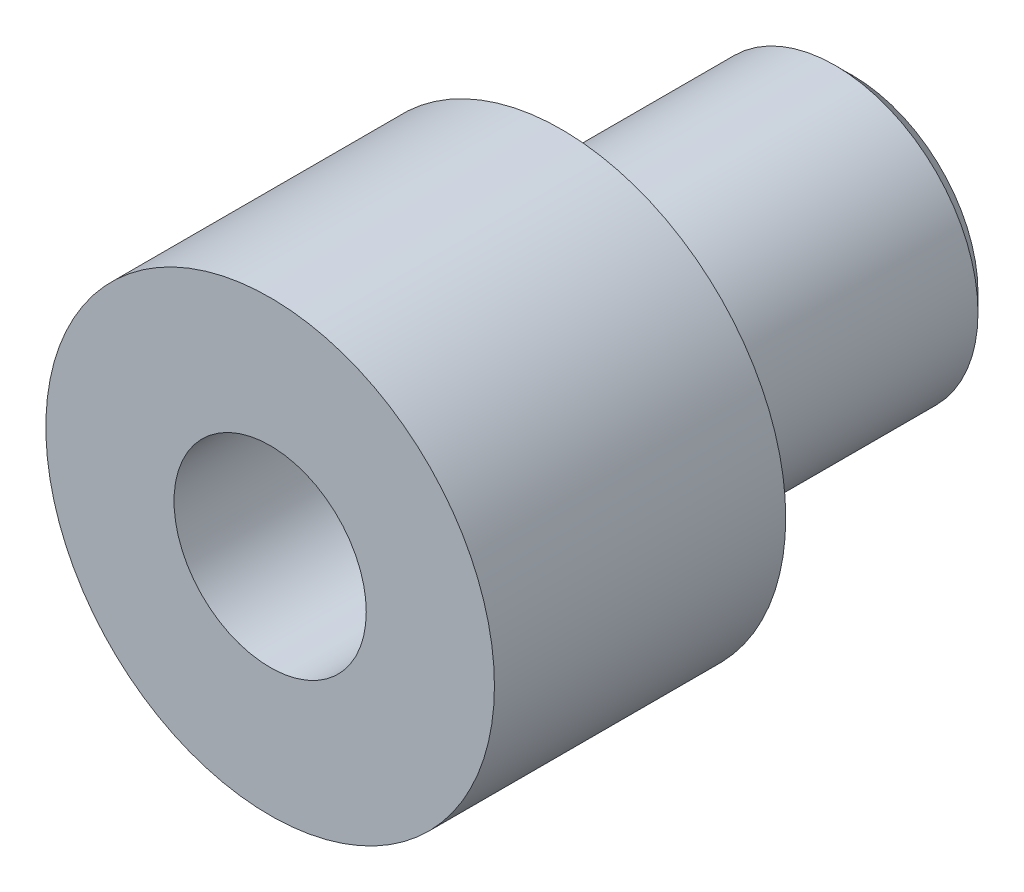
SolidWorks part; units mm, degrees
material "ABS PC"
ref_plane "Front Plane" through (0, 0, 0) normal (0, 0, 1) x (1, 0, 0)
ref_plane "Top Plane" through (0, 0, 0) normal (0, 1, 0) x (1, 0, 0)
ref_plane "Right Plane" through (0, 0, 0) normal (1, 0, 0) x (0, 0, -1)
sketch "Sketch1" plane through (0, 0, 0) normal (1, 0, 0) x (0, 0, -1)
  line L0 (0, 1.65) -> (0, 3.85)
  line L1 (0, 3.85) -> (5, 3.85)
  line L2 (5, 3.85) -> (5, 2.45)
  line L3 (5, 2.45) -> (10, 2.45)
  line L4 (10, 2.45) -> (10, 1.65)
  line L5 (0, 1.65) -> (10, 1.65)
  line L6 (0, 0) -> (10, 0) construction
  dimension "D1" = 3.3
  dimension "D2" = 4.9
  dimension "D3" = 7.7
  dimension "D4" = 5
  dimension "D5" = 5
revolve "Revolve1" add sketch "Sketch1" angle 360 about L6
chamfer "Chamfer1" distance 0.3 angle 45 1 edges at (2.45, 0, -10)
move or copy body "Body-Move/Copy1" [suppressed] bodies to move or copy 101
